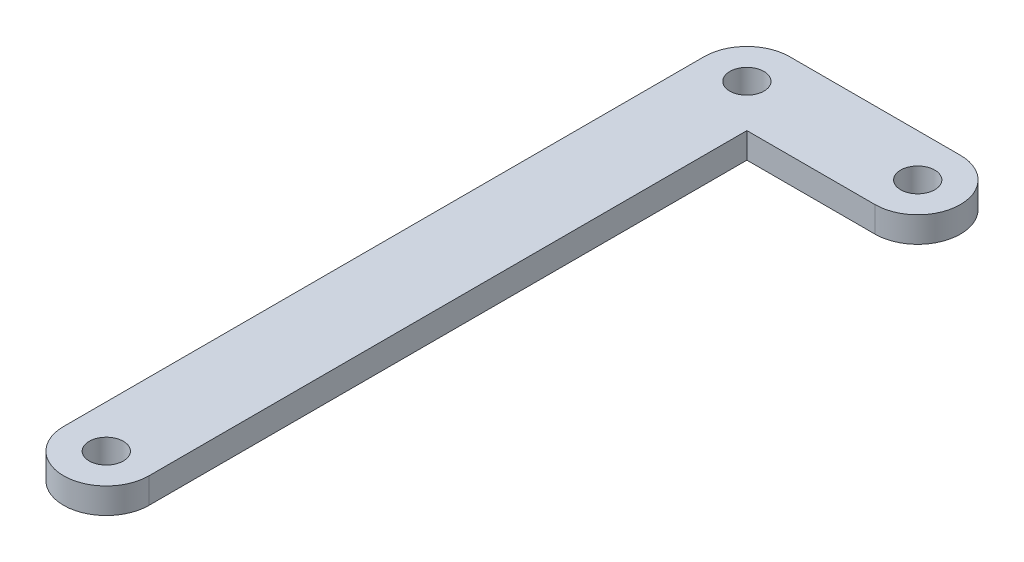
SolidWorks part; units mm, degrees
ref_plane "Front Plane" through (0, 0, 0) normal (0, 0, 1) x (1, 0, 0)
ref_plane "Top Plane" through (0, 0, 0) normal (0, 1, 0) x (1, 0, 0)
ref_plane "Right Plane" through (0, 0, 0) normal (1, 0, 0) x (0, 0, -1)
sketch "Sketch1" plane through (0, 0, 0) normal (0, 1, 0) x (1, 0, 0)
  line L7 (19.0688, -48.4258) -> (19.0688, 26.5742)
  line L8 (19.0688, 26.5742) -> (29.0688, 26.5742)
  line L9 (29.0688, -48.4258) -> (29.0688, 26.5742)
  line L10 (24.0688, 31.5742) -> (44.0688, 31.5742)
  line L11 (24.0688, 31.5742) -> (24.0688, 21.5742)
  line L12 (24.0688, 21.5742) -> (44.0688, 21.5742)
  arc A5 (19.0688, -48.4258) -> (29.0688, -48.4258) centre (24.0688, -48.4258) ccw
  circle A6 centre (24.0688, -48.4258) radius 2
  arc A7 (44.0688, 31.5742) -> (44.0688, 21.5742) centre (44.0688, 26.5742) cw
  circle A8 centre (44.0688, 26.5742) radius 2
  arc A9 (24.0688, 31.5742) -> (19.0688, 26.5742) centre (24.0688, 26.5742) ccw
  circle A10 centre (24.0688, 26.5742) radius 2
  point P17 (29.0688, 21.5742)
  point P24 (29.0688, 21.5742)
  dimension "D4" = 75
  dimension "D7" = 4
  dimension "D11" = 4
  dimension "D13" = 4
  dimension "D6" = 10
  dimension "D8" = 70
  dimension "D9" = 20
  dimension "D10" = 10
  dimension "D12" = 15
extrude "Boss-Extrude1" add sketch "Sketch1" along normal blind 3 contours A10 L8 L7 A5 L9 L12 L11 A6 | A10 L8 L9 L12 A7 L10 L11 A8 | A10 L11 L12 L9 L8 | A10 L11 A9 L8 region at (23.9888, 0, 13.6976) region at (21.7042, 0, -28.9388) region at (36.9224, 0, -26.8756) region at (26.8061, 0, -23.8369)
